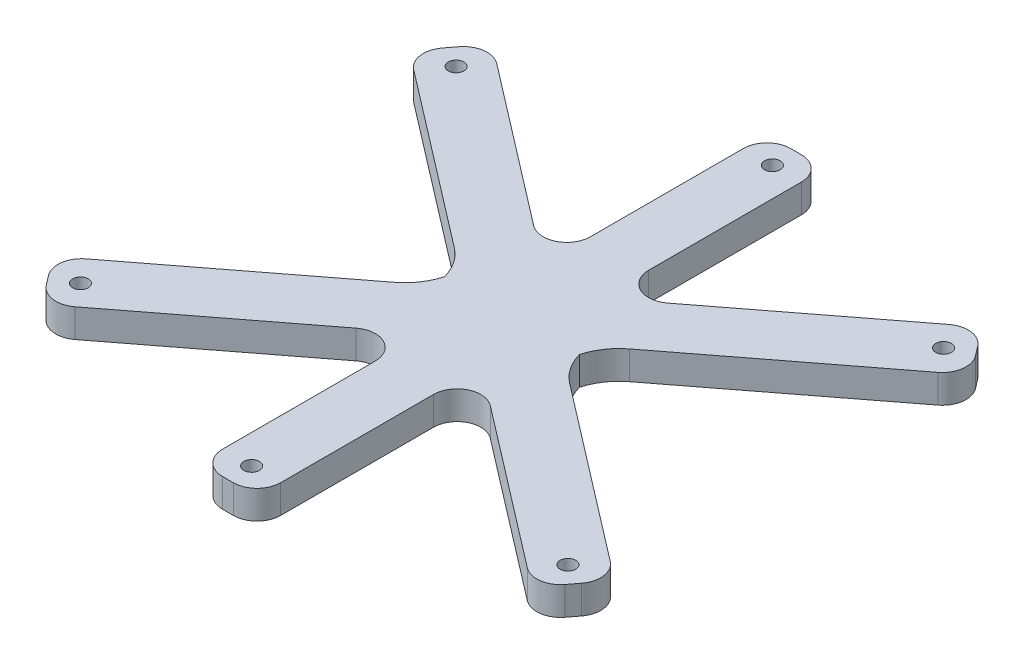
SolidWorks part; units mm, degrees
ref_plane "Front Plane" through (0, 0, 0) normal (0, 0, 1) x (1, 0, 0)
ref_plane "Top Plane" through (0, 0, 0) normal (0, 1, 0) x (1, 0, 0)
ref_plane "Right Plane" through (0, 0, 0) normal (1, 0, 0) x (0, 0, -1)
sketch "Sketch1" plane through (0, 0, 0) normal (0, 1, 0) x (1, 0, 0)
  circle A0 centre (0, 0) radius 14
  dimension "D1" = 28
extrude "Boss-Extrude1" add sketch "Sketch1" along normal blind 6
sketch "Sketch2" plane through (0, 0, 0) normal (0, 1, 0) x (1, 0, 0)
  line L0 (-13.7435, 2.6678) -> (-59.3395, 37.6548)
  line L1 (0.2695, -0.2068) -> (-63.7589, 48.924) construction
  line L2 (-51.73, 47.5718) -> (-6.134, 12.5847)
  line L3 (0, 37.6664) -> (0, -25.0328) construction
  line L4 (-51.73, 47.5718) -> (-59.3395, 37.6548)
  circle A0 centre (0, 0) radius 14 construction
  arc A1 (-6.134, 12.5847) -> (-13.7435, 2.6678) centre (0, 0) ccw
  point P9 (-55.5347, 42.6133)
  dimension "D1" = 70
  dimension "D2" = 52.5
  dimension "D3" = 12.5
extrude "Boss-Extrude2" add sketch "Sketch2" along normal up to surface (6 mm away) up to face at (0, 6, 14)
mirror "Mirror1" about plane through (0, 0, 0) normal (1, 0, 0) of "Boss-Extrude2"
mirror "Mirror2" about plane through (0, 0, 0) normal (0, 0, 1) of "Mirror1", "Boss-Extrude2"
sketch "Sketch4" plane through (0, 6, 0) normal (0, 1, 0) x (1, 0, 0)
  line L0 (0, 65.599) -> (0, -44.8835) construction
  line L1 (-6.134, 60) -> (-6.134, 12.5847)
  line L2 (-6.134, 60) -> (6.134, 60)
  line L3 (6.134, 60) -> (6.134, 12.5847)
  arc A2 (6.134, 12.5847) -> (-6.134, 12.5847) centre (0, 0) ccw construction
  arc A3 (6.134, 12.5847) -> (-6.134, 12.5847) centre (0, 0) ccw
  point P1 (0, 0)
  point P8 (0, 60)
  point P12 (0, 0)
  point P13 (0, 0)
  point P14 (0, 0)
  point P15 (6.134, 12.5847)
  dimension "D2" = 60
extrude "Boss-Extrude4" add sketch "Sketch4" against normal up to surface (6 mm away) up to face at (0, 0, 0)
mirror "Mirror6" about plane through (0, 0, 0) normal (0, 0, 1) of "Boss-Extrude4"
fillet "Fillet4" radius 5 4 edges at (6.134, 3, 12.5847) (-6.134, 3, 12.5847) (6.134, 3, -12.5847) (-6.134, 3, -12.5847)
fillet "Fillet5" radius 12 4 edges at (-13.7435, 3, 2.6678) (-13.7435, 3, -2.6678) (13.7435, 3, 2.6678) (13.7435, 3, -2.6678)
sketch "Sketch3" plane through (0, 6, 0) normal (0, 1, 0) x (1, 0, 0)
  line L0 (1.091, 1.4657) -> (-89.0465, 66.965) construction
  line L1 (-51.73, 47.5718) -> (-59.3395, 37.6548) construction
  circle A0 centre (-51.4885, 39.6731) radius 1.65
  point P3 (-46.9598, 36.0335)
  point P7 (-55.5347, 42.6133)
  dimension "D1" = 3.3
  dimension "D2" = 5
extrude "Cut-Extrude1" cut sketch "Sketch3" against normal through all
mirror "Mirror3" about plane through (0, 0, 0) normal (1, 0, 0) of "Cut-Extrude1"
mirror "Mirror4" about plane through (0, 0, 0) normal (0, 0, 1) of "Mirror3", "Cut-Extrude1"
sketch "Sketch5" plane through (0, 6, 0) normal (0, 1, 0) x (1, 0, 0)
  line L0 (6.134, 60) -> (-6.134, 60) construction
  circle A0 centre (0, 55) radius 1.65
  dimension "D1" = 3.3
  dimension "D2" = 5
extrude "Cut-Extrude2" cut sketch "Sketch5" against normal through all
mirror "Mirror7" about plane through (0, 0, 0) normal (0, 0, 1) of "Cut-Extrude2"
fillet "Fillet3" radius 5 12 edges at (51.73, 3, 47.5718) (59.3395, 3, 37.6548) (59.3395, 3, -37.6548) (51.73, 3, -47.5718) (-51.73, 3, -47.5718) (-59.3395, 3, -37.6548) (-59.3395, 3, 37.6548) (-51.73, 3, 47.5718) (-6.134, 3, -60) (6.134, 3, -60) (-6.134, 3, 60) (6.134, 3, 60)
